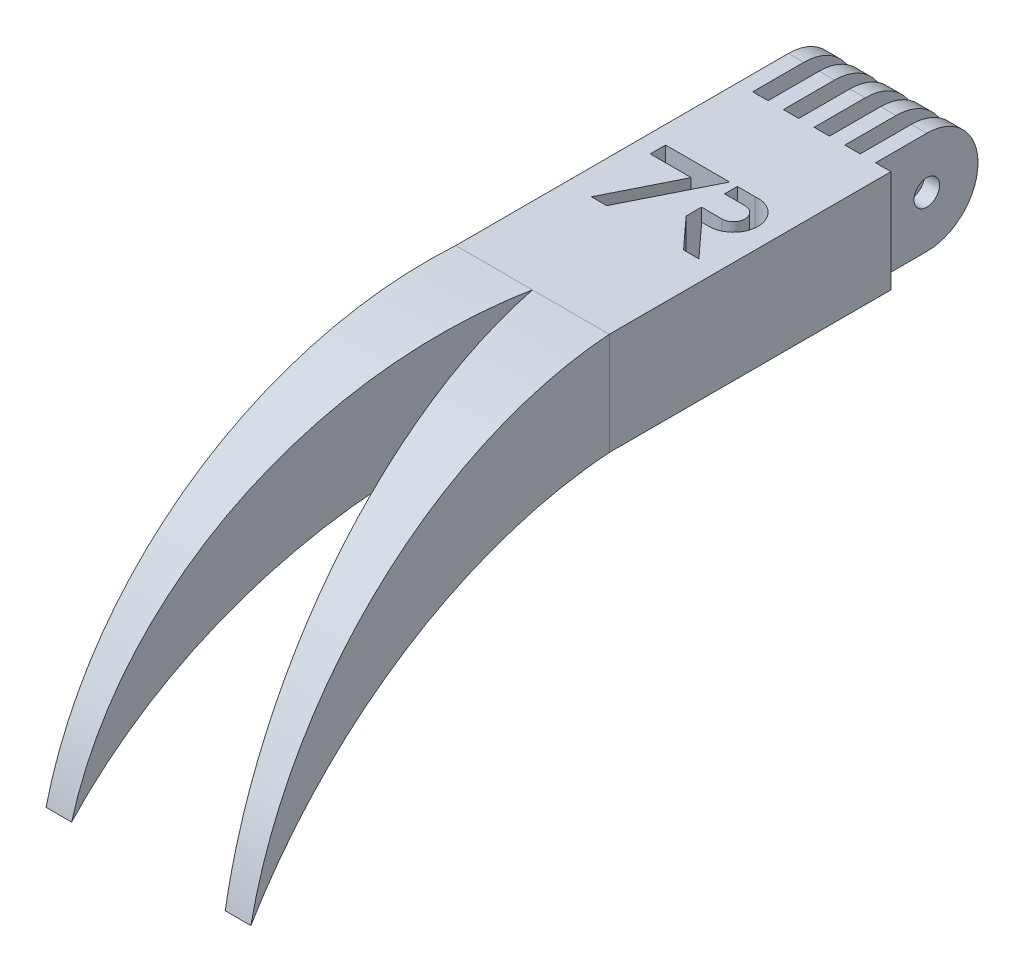
SolidWorks part; units mm, degrees
ref_plane "Plan de face" through (0, 0, 0) normal (0, 0, 1) x (1, 0, 0)
ref_plane "Plan de dessus" through (0, 0, 0) normal (0, 1, 0) x (1, 0, 0)
ref_plane "Plan de droite" through (0, 0, 0) normal (1, 0, 0) x (0, 0, -1)
sketch "Esquisse1" plane through (0, 0, 0) normal (1, 0, 0) x (0, 0, -1)
  line L1 (0, 10) -> (75, 10)
  line L2 (75, 10) -> (75, 30)
  line L3 (75, 30) -> (0, 30)
  arc A0 (0, 10) -> (-75, -30) centre (0, -80.3125) ccw
  arc A1 (0, 30) -> (-75, -30) centre (0, -46.875) ccw
  circle A2 centre (65, 20) radius 2.5
  dimension "D8" = 5
  dimension "D1" = 10
  dimension "D2" = 20
  dimension "D3" = 75
  dimension "D4" = 75
  dimension "D5" = 75
  dimension "D6" = 75
  dimension "D7" = 30
  dimension "D9" = 10
  dimension "D10" = 10
extrude "Boss.-Extru.1" add sketch "Esquisse1" along normal blind 40
sketch "Esquisse2" plane through (0, 30, 0) normal (0, 1, 0) x (1, 0, 0)
  line L0 (20, 0) -> (5, -75)
  line L1 (40, 0) -> (0, 0) construction
  line L2 (5, -75) -> (35, -75)
  line L3 (35, -75) -> (20, 0)
  line L4 (0, 75) -> (5, 75)
  line L5 (40, 75) -> (0, 75) construction
  line L6 (5, 75) -> (5, 0)
  line L7 (5, 0) -> (0, -75)
  line L8 (0, -75) -> (0, 75)
  line L9 (40, 75) -> (35, 75)
  line L10 (35, 75) -> (35, 0)
  line L11 (35, 0) -> (40, -75)
  line L12 (40, -75) -> (40, 75)
  dimension "D1" = 30
  dimension "D2" = 5
extrude "Enlèv. mat.-Extru.1" cut sketch "Esquisse2" against normal blind 60
fillet "Congé1" radius 10 2 edges at (20, 10, -75) (20, 30, -75)
sketch "Esquisse3" plane through (0, 30, 0) normal (0, 1, 0) x (1, 0, 0)
  line L0 (35, 82) -> (35, 55)
  line L1 (35, 65) -> (35, 0) construction
  line L2 (35, 55) -> (32, 55)
  line L3 (32, 55) -> (32, 80)
  line L4 (32, 80) -> (29, 80)
  line L5 (29, 80) -> (29, 55)
  line L6 (29, 55) -> (26, 55)
  line L7 (26, 55) -> (26, 80)
  line L8 (26, 80) -> (23, 80)
  line L9 (23, 80) -> (23, 55)
  line L10 (23, 55) -> (20, 55)
  line L11 (20, 55) -> (20, 80)
  line L12 (20, 80) -> (17, 80)
  line L13 (17, 80) -> (17, 55)
  line L14 (17, 55) -> (14, 55)
  line L15 (14, 55) -> (14, 80)
  line L16 (14, 80) -> (11, 80)
  line L17 (11, 80) -> (11, 55)
  line L18 (11, 55) -> (8, 55)
  line L19 (8, 55) -> (8, 82)
  line L20 (8, 82) -> (35, 82)
  line L21 (5, 75) -> (35, 75) construction
  dimension "D1" = 3
  dimension "D2" = 3
  dimension "D3" = 3
  dimension "D4" = 3
  dimension "D5" = 3
  dimension "D6" = 3
  dimension "D7" = 3
  dimension "D8" = 3
  dimension "D9" = 3
  dimension "D10" = 20
  dimension "D11" = 25
  dimension "D12" = 27
  dimension "D13" = 25
  dimension "D14" = 25
  dimension "D15" = 25
  dimension "D16" = 25
  dimension "D17" = 25
  dimension "D18" = 25
  dimension "D19" = 25
extrude "Enlèv. mat.-Extru.2" cut sketch "Esquisse3" against normal blind 20
sketch "Esquisse4" plane through (0, 30, 0) normal (0, 1, 0) x (1, 0, 0)
  line L0 (8.5, 37.5) -> (8.5, 34.5)
  line L1 (8.5, 34.5) -> (16.5, 34.5)
  line L2 (16.5, 34.5) -> (10, 21.5)
  line L3 (10, 21.5) -> (13, 21.5)
  line L4 (13, 21.5) -> (21, 37.5)
  line L5 (21, 37.5) -> (8.5, 37.5)
  line L6 (31, 21.5) -> (28, 21.5)
  line L7 (28, 21.5) -> (22.5, 27.5)
  line L8 (22.5, 27.5) -> (22.5, 30.5)
  line L9 (22.5, 30.5) -> (26.5, 30.5)
  line L10 (22.5, 37.5) -> (22.5, 35)
  line L11 (5, 0) -> (5, 65) construction
  line L12 (8, 55) -> (11, 55) construction
  line L13 (22.5, 35) -> (26.5, 35)
  line L14 (22.5, 37.5) -> (26, 37.5)
  line L15 (31, 21.5) -> (25.0657, 27.9738)
  line L16 (26, 55) -> (29, 55) construction
  line L17 (35, 55) -> (35, 0) construction
  line L18 (26.5, 27.9738) -> (25.0657, 27.9738)
  arc A0 (26.5, 35) -> (26.5, 30.5) centre (26.5, 32.75) cw
  arc A1 (26, 37.5) -> (26.5, 27.9738) centre (26.5, 32.75) cw
  dimension "D1" = 3
  dimension "D2" = 3
  dimension "D3" = 8
  dimension "D4" = 3.5
  dimension "D5" = 17.5
  dimension "D6" = 13
  dimension "D7" = 12.5
  dimension "D8" = 2.5
  dimension "D9" = 17.5
  dimension "D10" = 12.5
  dimension "D11" = 3
  dimension "D12" = 4.5
  dimension "D13" = 3.5
  dimension "D14" = 4
  dimension "D15" = 4
  dimension "D16" = 3
extrude "Enlèv. mat.-Extru.3" cut sketch "Esquisse4" against normal blind 20
